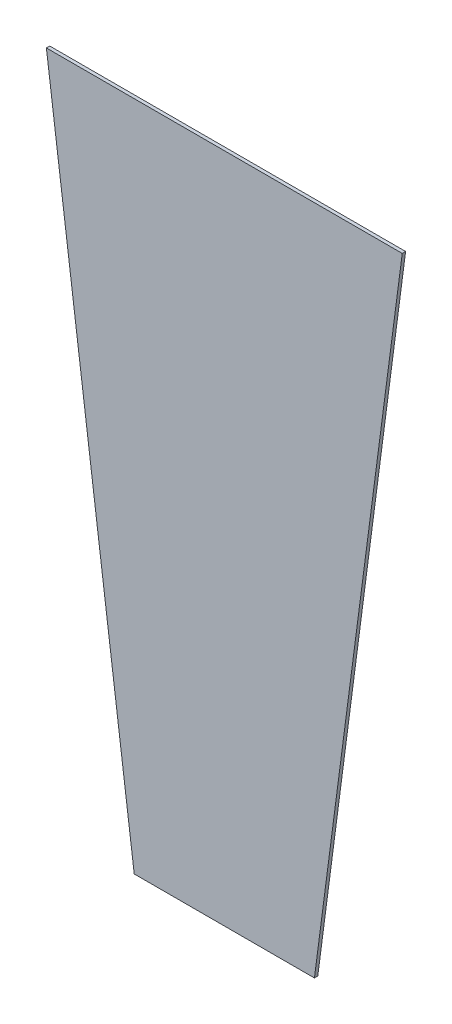
SolidWorks part; units mm, degrees
material "201 Annealed Stainless Steel (SS)"
ref_plane "Front Plane" through (0, 0, 0) normal (0, 0, 1) x (1, 0, 0)
ref_plane "Top Plane" through (0, 0, 0) normal (0, 1, 0) x (1, 0, 0)
ref_plane "Right Plane" through (0, 0, 0) normal (1, 0, 0) x (0, 0, -1)
sketch "Sketch1" plane through (0, 0, 0) normal (0, 0, 1) x (1, 0, 0)
  line L1 (-106, -200) -> (106, -200)
  line L2 (-106, -200) -> (-106, 200)
  line L3 (-106, 200) -> (106, 200)
  line L4 (106, -200) -> (106, 200)
  line L5 (-106, -200) -> (106, 200) construction
  line L6 (-106, 200) -> (106, -200) construction
  point P0 (0, 0)
  dimension "D1" = 212
  dimension "D2" = 400
extrude "Boss-Extrude1" add sketch "Sketch1" along normal blind 2
sketch "Sketch2" plane through (0, 0, 0) normal (0, 0, -1) x (-1, 0, 0)
  line L5 (53.6751, -200) -> (106, 200)
  line L12 (106, 200) -> (106, -200)
  line L13 (106, -200) -> (53.6751, -200)
  line L14 (106, -200) -> (-106, -200) construction
  line L15 (106, -200) -> (106, 200) construction
  line L16 (106, 200) -> (-106, 200) construction
  line L17 (0, 0) -> (0, -70.9837) construction
  line L18 (0, -236.558) -> (0, 85.0831) construction
  line L19 (-106, -200) -> (-53.6751, -200)
  line L20 (-106, 200) -> (-106, -200)
  line L21 (-53.6751, -200) -> (-106, 200)
extrude "Cut-Extrude1" cut sketch "Sketch2" against normal through all
sketch "Sketch3" [suppressed] plane through (49, 0, 0) normal (1, 0, 0) x (0, 0, -1)
  circle A0 centre (-6.722, 55.3681) radius 5.3835
surface "Surface-Extrude1" [suppressed] sketch "Sketch3"
sketch "Sketch4" [suppressed] plane through (-49, 0, 0) normal (-1, 0, 0) x (0, 0, 1)
  line L1 (2, 80) -> (0, 80) construction
  line L2 (0, -80) -> (0, 80) construction
  point P0 (7.5, 76)
  dimension "D1" = 4
  dimension "D2" = 7.5
ref_axis "Axis1" [suppressed] through (-49, 76, 7.5) along (1, 0, 0)
sketch "Sketch5" [suppressed] plane through (0, 0, 0) normal (0, 0, -1) x (-1, 0, 0)
  line L0 (49, 80) -> (49, -80) construction
  line L1 (-49, 80) -> (49, 80)
  line L2 (-49, 80) -> (-49, 60.2594)
  line L3 (-49, 60.2594) -> (49, 60.2594)
  line L4 (49, 80) -> (49, 60.2594)
extrude "Cut-Extrude2" [suppressed] cut sketch "Sketch5" against normal blind 3
